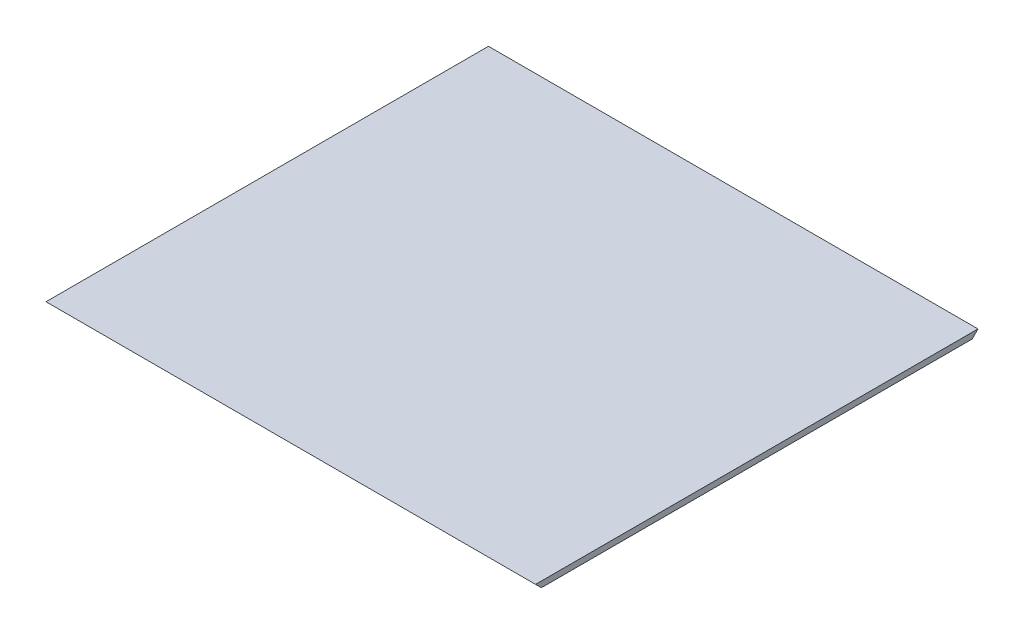
SolidWorks part; units mm, degrees
ref_plane "Front Plane" through (0, 0, 0) normal (0, 0, 1) x (1, 0, 0)
ref_plane "Top Plane" through (0, 0, 0) normal (0, 1, 0) x (1, 0, 0)
ref_plane "Right Plane" through (0, 0, 0) normal (1, 0, 0) x (0, 0, -1)
sketch "Sketch1" plane through (0, 0, 0) normal (0, 1, 0) x (1, 0, 0)
  line L1 (-133.35, -120.523) -> (133.35, -120.523)
  line L2 (-133.35, -120.523) -> (-133.35, 120.523)
  line L3 (-133.35, 120.523) -> (133.35, 120.523)
  line L4 (133.35, -120.523) -> (133.35, 120.523)
  line L5 (-133.35, -120.523) -> (133.35, 120.523) construction
  line L6 (-133.35, 120.523) -> (133.35, -120.523) construction
  point P0 (0, 0)
  dimension "D1" = 241.046
  dimension "D2" = 266.7
extrude "Boss-Extrude1" add sketch "Sketch1" along normal mid plane 3.175 contours L2 L3 L4 L1
sketch "Sketch3" plane through (-133.35, 0, 0) normal (-1, 0, 0) x (0, 0, 1)
  line L0 (120.523, 1.5875) -> (117.3168, -1.5875)
  line L2 (120.523, -1.5875) -> (-120.523, -1.5875) construction
  line L3 (117.3168, -1.5875) -> (119.1808, -3.4699)
  line L4 (119.1808, -3.4699) -> (122.387, -0.2949)
  line L5 (-120.523, 1.5875) -> (-115.9365, -2.999)
  line L6 (-115.9365, -2.999) -> (-119.2194, -6.282)
  line L7 (-119.2194, -6.282) -> (-123.806, -1.6955)
  line L8 (-123.806, -1.6955) -> (-120.523, 1.5875)
  line L9 (122.387, -0.2949) -> (120.523, 1.5875)
extrude "Cut-Extrude2" cut sketch "Sketch3" against normal through all
